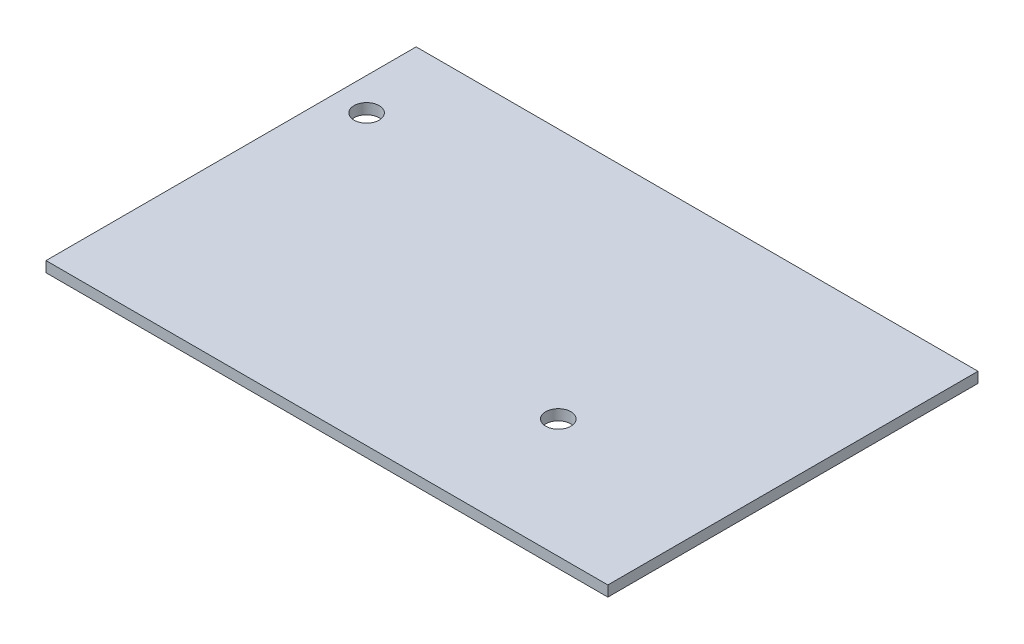
SolidWorks part; units mm, degrees
material "ABS PC"
ref_plane "Front Plane" through (0, 0, 0) normal (0, 0, 1) x (1, 0, 0)
ref_plane "Top Plane" through (0, 0, 0) normal (0, 1, 0) x (1, 0, 0)
ref_plane "Right Plane" through (0, 0, 0) normal (1, 0, 0) x (0, 0, -1)
sketch "Sketch1" plane through (0, 0, 0) normal (0, 1, 0) x (1, 0, 0)
  line L1 (85, 56) -> (0, 56)
  line L2 (85, 56) -> (85, 0)
  line L3 (85, 0) -> (0, 0)
  line L4 (0, 56) -> (0, 0)
  circle A0 centre (59.5, 18) radius 1.905
  circle A1 centre (4.9, 43.6) radius 1.905
  dimension "D7" = 3.81
  dimension "D8" = 3.81
  dimension "D1" = 85
  dimension "D2" = 56
  dimension "D3" = 25.5
  dimension "D4" = 18
  dimension "D5" = 12.4
  dimension "D6" = 4.9
extrude "Printplaat" add sketch "Sketch1" along normal blind 1.6
